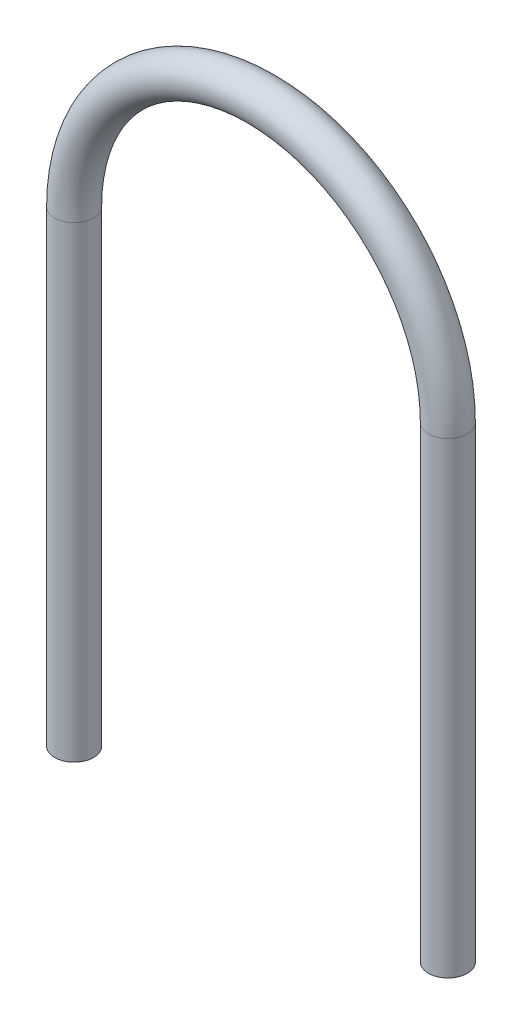
SolidWorks part; units mm, degrees
material "AISI 1020"
ref_plane "Front Plane" through (0, 0, 0) normal (0, 0, 1) x (1, 0, 0)
ref_plane "Top Plane" through (0, 0, 0) normal (0, 1, 0) x (1, 0, 0)
ref_plane "Right Plane" through (0, 0, 0) normal (1, 0, 0) x (0, 0, -1)
sketch "Sketch1" plane through (0, 0, 0) normal (0, 0, 1) x (1, 0, 0)
  line L0 (0, 0) -> (0, 76.2)
  line L1 (-54.61, 76.2) -> (-54.61, 0)
  arc A0 (0, 76.2) -> (-54.61, 76.2) centre (-27.305, 76.2) ccw
  dimension "D1" = 27.305
sketch "Sketch2" plane through (0, 0, 0) normal (0, 1, 0) x (1, 0, 0)
  line L0 (0, 0) -> (3.175, 0) construction
  circle A0 centre (3.175, 0) radius 3.175
  dimension "D1" = 6.35
sweep "Sweep1" add profiles "Sketch2" path "Sketch1"
ref_plane "Plane1" through (0, 76.2, 0) normal (0, -1, 0) x (1, 0, 0)
sketch "Sketch3" plane through (0, 76.2, 0) normal (0, -1, 0) x (1, 0, 0)
  line L0 (0, 0) -> (0, -2.2894)
  line L1 (0, -2.2894) -> (0.1416, -2.2894)
  line L2 (0.1416, -2.2894) -> (0.1416, 2.0391)
  line L3 (0.1416, 2.0391) -> (0, 2.0391)
  line L4 (0, 2.0391) -> (0, 0)
sketch "Sketch4" plane through (0, 0, 0) normal (0, 0, 1) x (1, 0, 0)
  line L0 (-54.61, 76.2) -> (0, 76.2) construction
  point P0 (-27.305, 76.2)
  point P5 (-27.305, 76.2)
sketch "Sketch5" plane through (0, 76.2, 0) normal (0, -1, 0) x (1, 0, 0)
  line L0 (-27.305, 0) -> (-27.305, -8.0467) construction
  line L1 (-54.61, 0) -> (0, 0) construction
